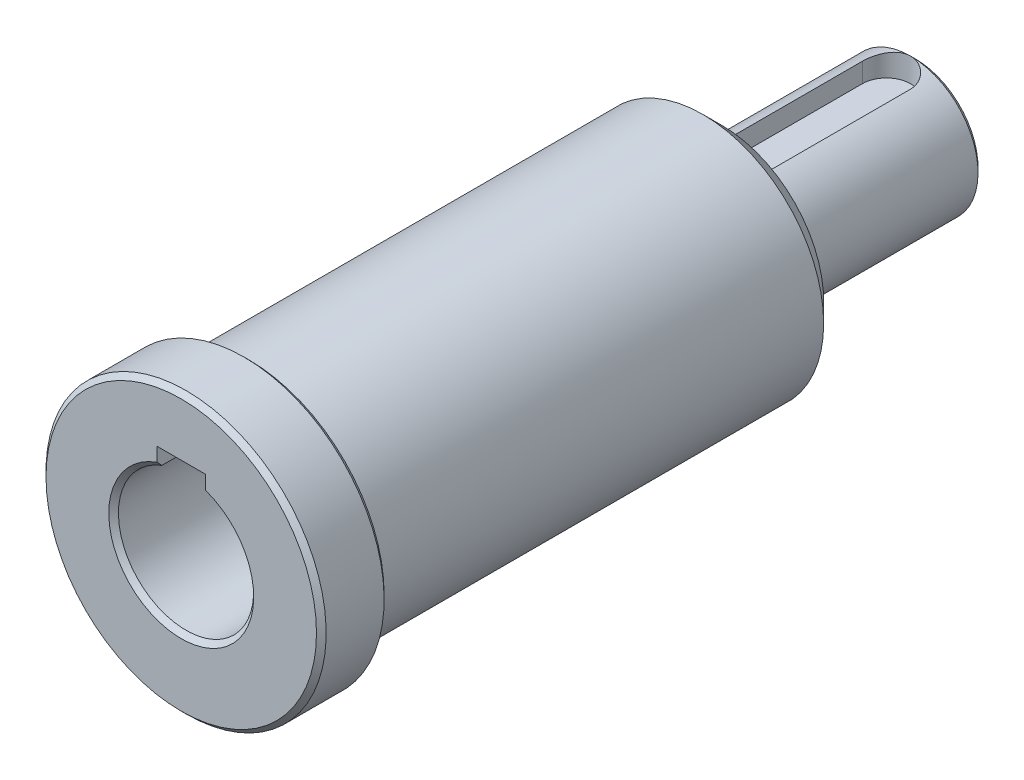
SolidWorks part; units mm, degrees
ref_plane "前视基准面" through (0, 0, 0) normal (0, 0, 1) x (1, 0, 0)
ref_plane "上视基准面" through (0, 0, 0) normal (0, 1, 0) x (1, 0, 0)
ref_plane "右视基准面" through (0, 0, 0) normal (1, 0, 0) x (0, 0, -1)
other "Configuration Table"
sketch "草图1" plane through (0, 0, 0) normal (1, 0, 0) x (0, 0, -1)
  line L0 (0, 0) -> (0, 14.5)
  line L1 (0, 14.5) -> (7, 14.5)
  line L2 (7, 14.5) -> (7, 12.5)
  line L3 (7, 12.5) -> (56, 12.5)
  line L4 (56, 12.5) -> (56, 6.98)
  line L5 (56, 6.98) -> (76, 6.98)
  line L6 (76, 6.98) -> (76, 0)
  line L7 (76, 0) -> (0, 0)
  dimension "D1" = 14.5
  dimension "D2" = 12.5
  dimension "D3" = 6.98
  dimension "D4" = 49
  dimension "D5" = 56
  dimension "D6" = 20
revolve "旋转1" add sketch "草图1" angle 360 about L7
sketch "草图3" plane through (0, 0, 0) normal (1, 0, 0) x (0, 0, -1)
  line L0 (0, 0) -> (0, 7)
  line L1 (0, 14.5) -> (0, -14.5) construction
  line L2 (0, 7) -> (33.5, 7)
  line L3 (33.5, 7) -> (33.5, 2.75)
  line L4 (33.5, 2.75) -> (76, 2.75)
  line L5 (76, -6.98) -> (76, 6.98) construction
  line L6 (76, 2.75) -> (76, 0)
  line L7 (76, 0) -> (0, 0)
  dimension "D1" = 7
  dimension "D2" = 2.75
  dimension "D3" = 33.5
revolve "切除-旋转1" cut sketch "草图3" angle 360 about L7
fillet "圆角1" radius 1 1 edges at (0, 7, -33.5)
chamfer "倒角1" distance 0.5 angle 45 6 edges at (0, 2.75, -76) (0, 6.98, -76) (0, 14.5, 0) (0, 7, 0) (0, 14.5, -7) (0, 2.75, -33.5)
chamfer "倒角2" distance 2 angle 45 1 edges at (0, 12.5, -56)
sketch "草图4" plane through (0, 0, 0) normal (0, 0, 1) x (1, 0, 0)
  line L1 (-2.5, 8.5) -> (2.5, 8.5)
  line L2 (-2.5, 8.5) -> (-2.5, 0)
  line L3 (-2.5, 0) -> (2.5, 0)
  line L4 (2.5, 8.5) -> (2.5, 0)
  line L5 (-2.5, 8.5) -> (2.5, 0) construction
  line L6 (-2.5, 0) -> (2.5, 8.5) construction
  circle A1 centre (0, 0) radius 7.5 construction
  point P0 (0, 4.25)
  dimension "D1" = 5
  dimension "D2" = 16
extrude "切除-拉伸1" cut sketch "草图4" against normal blind 30
ref_plane "基准面1" through (0, 4.5, 0) normal (0, 1, 0) x (1, 0, 0)
sketch "草图5" plane through (0, 4.5, 0) normal (0, 1, 0) x (1, 0, 0)
  line L0 (0, 73) -> (0, 58.5) construction
  line L5 (2.5, 73) -> (2.5, 58.5)
  line L6 (-2.5, 73) -> (-2.5, 58.5)
  line L7 (-6.98, 75.5) -> (6.98, 75.5) construction
  line L8 (10.5, 56) -> (-10.5, 56) construction
  arc A2 (2.5, 73) -> (-2.5, 73) centre (0, 73) ccw
  arc A3 (-2.5, 58.5) -> (2.5, 58.5) centre (0, 58.5) ccw
  point P2 (0, 65.75)
  dimension "D1" = 5
extrude "切除-拉伸2" cut sketch "草图5" along normal through all
